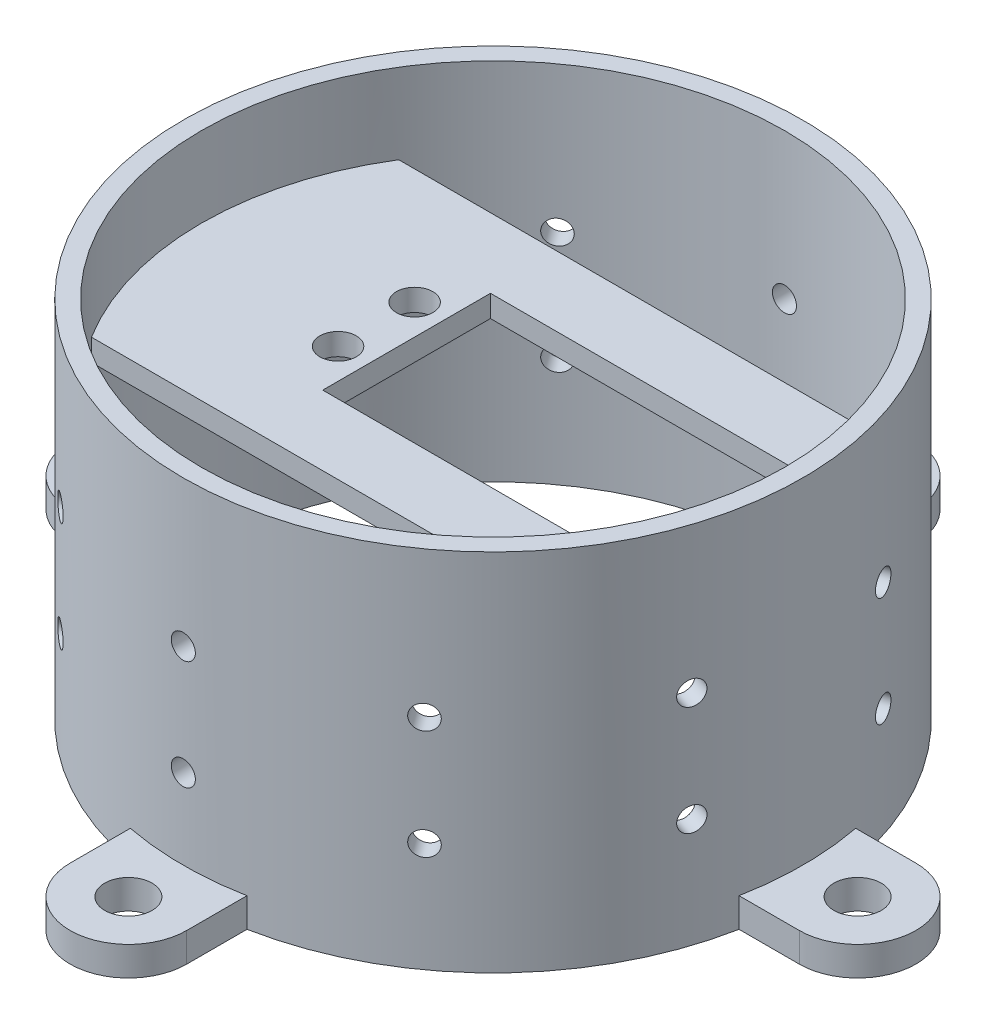
SolidWorks part; units mm, degrees
ref_plane "Front Plane" through (0, 0, 0) normal (0, 0, 1) x (1, 0, 0)
ref_plane "Top Plane" through (0, 0, 0) normal (0, 1, 0) x (1, 0, 0)
ref_plane "Right Plane" through (0, 0, 0) normal (1, 0, 0) x (0, 0, -1)
sketch "Sketch1" plane through (0, 0, 0) normal (0, 1, 0) x (1, 0, 0)
  circle A0 centre (0, 0) radius 40
  circle A1 centre (0, 0) radius 42.5
  dimension "D1" = 80
  dimension "D2" = 85
extrude "Boss-Extrude1" add sketch "Sketch1" along normal blind 50
sketch "Sketch2" plane through (0, 0, 0) normal (0, -1, 0) x (1, 0, 0)
  line L0 (42.5, 0) -> (50.0003, 0) construction
  line L1 (41.7403, 8) -> (50.0003, 8)
  line L2 (41.7403, -8) -> (50.0003, -8)
  circle A0 centre (0, 0) radius 42.5 construction
  circle A1 centre (50.0003, 0) radius 3.25
  arc A2 (50.0003, -8) -> (50.0003, 8) centre (50.0003, 0) ccw
  circle M3 centre (0, 0) radius 42.5
  dimension "D2" = 6.5
  dimension "D4" = 16
  dimension "D1" = 8.26
  dimension "D3" = 8
extrude "Boss-Extrude2" add sketch "Sketch2" against normal blind 4 contours L2 A2 L1 A1 M3 region at (45.8703, 0, 7.7719)
pattern_circular "CirPattern1" count 4 over 360 about axis through (0, 0, 0) along (0, 1, 0) of "Boss-Extrude2"
ref_plane "Plane1" through (0, 36, 0) normal (0, 1, 0) x (1, 0, 0)
sketch "Sketch4" plane through (0, 36, 0) normal (0, 1, 0) x (1, 0, 0)
  line L5 (34, -21.0713) -> (-34, -21.0713)
  line L7 (34, 21.0713) -> (-34, 21.0713)
  line L9 (34, -21.0713) -> (-34, 21.0713) construction
  line L10 (34, 21.0713) -> (-34, -21.0713) construction
  circle A3 centre (0, 0) radius 40 construction
  arc A4 (-34, 21.0713) -> (-34, -21.0713) centre (0, 0) ccw
  arc A5 (34, -21.0713) -> (34, 21.0713) centre (0, 0) ccw
  point P0 (0, 0)
  dimension "D1" = 68
extrude "Boss-Extrude3" add sketch "Sketch4" along normal blind 3
sketch "Sketch3" plane through (0, 39, 0) normal (0, 1, 0) x (1, 0, 0)
  line L0 (-15.9997, 5.25) -> (34.3003, 5.25) construction
  line L1 (-15.9997, 5.25) -> (-15.9997, -5.25) construction
  line L2 (-15.9997, -5.25) -> (34.3003, -5.25) construction
  line L3 (34.3003, 5.25) -> (34.3003, -5.25) construction
  line L4 (-15.9997, 5.25) -> (34.3003, -5.25) construction
  line L5 (34.3003, -5.25) -> (34.3003, 5.25) construction
  line L6 (34.3003, 5.25) -> (-15.9997, -5.25) construction
  line L7 (30.1503, -11.5) -> (-11.8497, -11.5)
  line L8 (30.1503, -11.5) -> (30.1503, 11.5)
  line L9 (30.1503, 11.5) -> (-11.8497, 11.5)
  line L10 (-11.8497, -11.5) -> (-11.8497, 11.5)
  line L11 (30.1503, -11.5) -> (-11.8497, 11.5) construction
  line L12 (30.1503, 11.5) -> (-11.8497, -11.5) construction
  line L13 (9.1503, 0) -> (50.0003, 0) construction
  circle A0 centre (34.3003, 5.25) radius 2.5
  circle A1 centre (34.3003, -5.25) radius 2.5
  circle A2 centre (-15.9997, -5.25) radius 2.5
  circle A3 centre (-15.9997, 5.25) radius 2.5
  circle A4 centre (9.1503, 0) radius 12.5 construction
  dimension "D1" = 5
  dimension "D4" = 25
  dimension "D2" = 10.5
  dimension "D3" = 50.3
  dimension "D5" = 42
  dimension "D6" = 23
  dimension "D7" = 40.85
extrude "Cut-Extrude1" cut sketch "Sketch3" against normal up to next
sketch "Sketch5" plane through (0, 0, 0) normal (0, 0, 1) x (1, 0, 0)
  line L0 (0, 0) -> (0, 36) construction
  line L1 (-60, 70) -> (40, 70)
  line L2 (-60, 70) -> (-60, 0)
  line L3 (-60, 0) -> (40, 0)
  line L4 (40, 70) -> (40, 0)
  line L5 (46.75, 36) -> (-46.75, 36) construction
  line L6 (-10, 0) -> (-10, 70) construction
  line L7 (8, 0) -> (41.7403, 0) construction
  circle A0 centre (-57, 67) radius 1.75
  circle A1 centre (35.33, 67) radius 1.75
  circle A2 centre (-57, 13.85) radius 1.75
  circle A3 centre (35.33, 13.85) radius 1.75
  dimension "D3" = 3.5
  dimension "D4" = 92.33
  dimension "D5" = 3
  dimension "D6" = 3
  dimension "D8" = 53.15
  dimension "D1" = 100
  dimension "D2" = 70
  dimension "D9" = 10
  dimension "D7" = 2
extrude "Boss-Extrude4" [suppressed] add sketch "Sketch5" along normal blind 2 from offset 42
fillet "Fillet1" [suppressed] radius 3
sketch "Sketch6" plane through (0, 0, 0) normal (0, 0, 1) x (1, 0, 0)
  line L0 (-41.7403, 0) -> (-8, 0) construction
  circle A0 centre (0, 15) radius 1.65
  circle A1 centre (0, 30) radius 1.65
  dimension "D1" = 15
  dimension "D2" = 3.3
  dimension "D3" = 15
extrude "Cut-Extrude2" cut sketch "Sketch6" against normal up to next and the other way up to next
pattern_circular "CirPattern2" count 6 every 36 about axis through (0, 50, 0) along (0, 1, 0) of "Cut-Extrude2"
